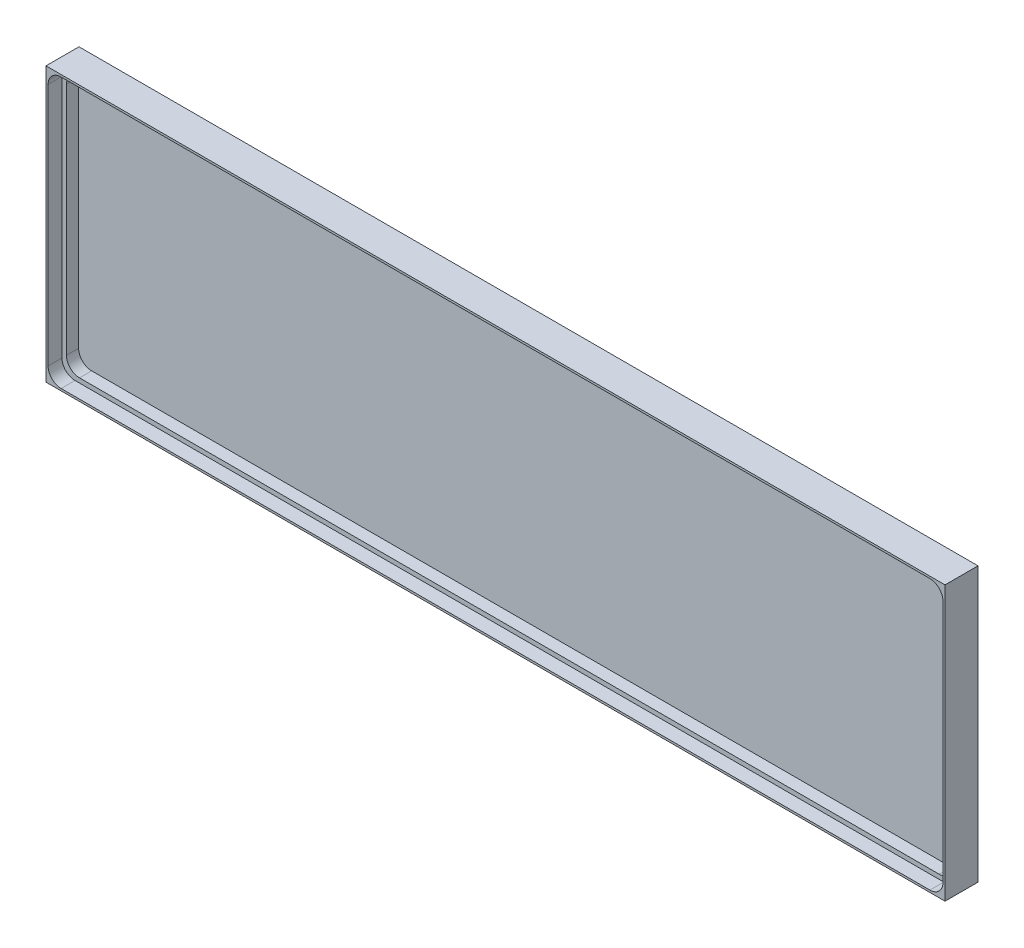
SolidWorks part; units mm, degrees
ref_plane "Front" through (0, 0, 0) normal (0, 0, 1) x (1, 0, 0)
ref_plane "Top" through (0, 0, 0) normal (0, 1, 0) x (1, 0, 0)
ref_plane "Right" through (0, 0, 0) normal (1, 0, 0) x (0, 0, -1)
sketch "Sketch1" plane through (0, 0, 0) normal (0, 0, 1) x (1, 0, 0)
  line L0 (164.4015, 50.1015) -> (-164.4015, 50.1015)
  line L1 (161.9885, -47.6885) -> (-161.9885, -47.6885)
  line L2 (161.9885, -47.6885) -> (161.9885, 47.6885)
  line L3 (161.9885, 47.6885) -> (-161.9885, 47.6885)
  line L4 (-161.9885, -47.6885) -> (-161.9885, 47.6885)
  line L5 (0, 47.6885) -> (0, -47.6885) construction
  line L6 (161.9885, 0) -> (-161.9885, 0) construction
  line L7 (163.6395, -49.3395) -> (-163.6395, -49.3395)
  line L8 (163.6395, -49.3395) -> (163.6395, 49.3395)
  line L9 (163.6395, 49.3395) -> (-163.6395, 49.3395)
  line L10 (-163.6395, -49.3395) -> (-163.6395, 49.3395)
  line L11 (0, 49.3395) -> (0, -49.3395) construction
  line L12 (163.6395, 0) -> (-163.6395, 0) construction
  line L13 (-164.4015, -50.1015) -> (-164.4015, 50.1015)
  line L14 (164.4015, -50.1015) -> (-164.4015, -50.1015)
  line L15 (164.4015, -50.1015) -> (164.4015, 50.1015)
  point P0 (0, 0)
  point P4 (0, 0)
  dimension "D1" = 95.377
  dimension "D2" = 323.977
  dimension "D3" = 1.651
  dimension "D4" = 1.651
  dimension "D5" = 0.762
extrude "Boss-Extrude1" add sketch "Sketch1" along normal blind 2.54 contours L4 L1 L2 L3 | L10 L7 L8 L9 L1 L4 L3 L2 | L14 L15 L0 L13 L7 L10 L9 L8 region at (164.0578, 0, 0) region at (0, 0, 0) region at (0, -48.9977, 0)
extrude "Boss-Extrude2" add sketch "Sketch1<3>" along normal blind 12.065 contours L14 L15 L0 L13 L7 L10 L9 L8 region at (164.0578, 0, 0)
sketch "Sketch1<3>" plane through (0, 0, 0) normal (0, 0, 1) x (1, 0, 0) same geometry as "Sketch1"
extrude "Boss-Extrude3" add sketch "Sketch1<4>" along normal offset from surface (6.985 mm away) 5.08 contours L10 L7 L8 L9 L1 L4 L3 L2 region at (0, -48.9977, 0) up to face at (0, 0, 12.065)
sketch "Sketch1<4>" plane through (0, 0, 0) normal (0, 0, 1) x (1, 0, 0) same geometry as "Sketch1"
fillet "Fillet1" radius 4.7625 8 edges at (-163.6395, -49.3395, 9.525) (-161.9885, -47.6885, 4.7625) (161.9885, -47.6885, 4.7625) (163.6395, -49.3395, 9.525) (161.9885, 47.6885, 4.7625) (163.6395, 49.3395, 9.525) (-161.9885, 47.6885, 4.7625) (-163.6395, 49.3395, 9.525)
